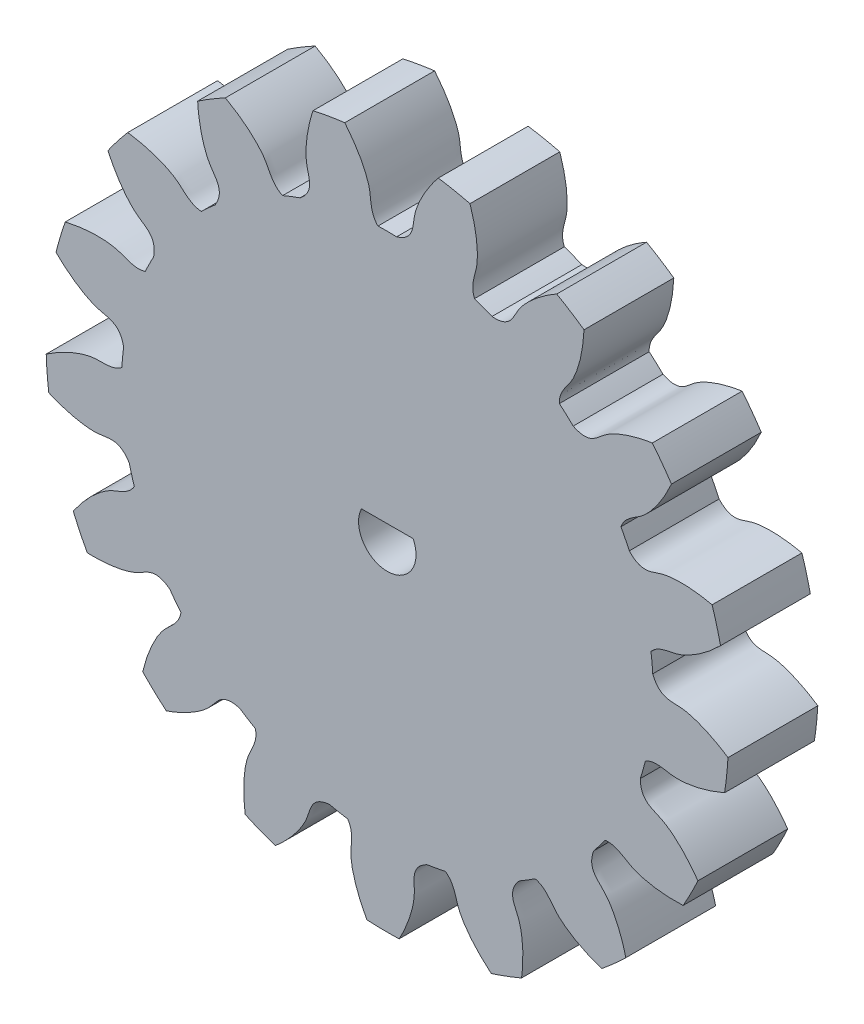
SolidWorks part; units mm, degrees
ref_plane "前视基准面" through (0, 0, 0) normal (0, 0, 1) x (1, 0, 0)
ref_plane "上视基准面" through (0, 0, 0) normal (0, 1, 0) x (1, 0, 0)
ref_plane "右视基准面" through (0, 0, 0) normal (1, 0, 0) x (0, 0, -1)
sketch "草图1" plane through (0, 0, 0) normal (0, 0, 1) x (1, 0, 0)
  circle A0 centre (0, 0) radius 19
  dimension "D1" = 38
extrude "凸台-拉伸1" add sketch "草图1" along normal blind 30
ref_axis "基准轴1" through (0, 0, -1.5) along (0, 0, 1)
sketch "草图2" plane through (0, 0, 0) normal (0, 0, 1) x (1, 0, 0)
  line L0 (0, 0) -> (0, 19) construction
  line L1 (-4.3413, 11.5) -> (4.3413, 11.5) construction
  circle A0 centre (0, 0) radius 19 construction
  arc A1 (0.5201, 14.7919) -> (-0.5201, 14.7919) centre (0, 0) ccw
  arc A2 (6.4873, 21.7509) -> (-6.0014, 21.8899) centre (0, 0) ccw
  spline S0 degree 3 poles (0.5201, 14.7919) (1.5309, 15.0929) (1.3911, 15.7825) (1.541, 16.4272) (1.5544, 16.4798) (1.5705, 16.5384) (1.5895, 16.6027) (1.6118, 16.6727) (1.6375, 16.7483) (1.667, 16.8294) (1.7003, 16.9159) (1.7378, 17.0076) (1.7796, 17.1044) (1.826, 17.2061) (1.8772, 17.3127) (1.9334, 17.4239) (1.9948, 17.5396) (2.0616, 17.6597) (2.134, 17.7839) (2.2122, 17.9121) (2.2964, 18.044) (2.3868, 18.1796) (2.4835, 18.3187) (2.5867, 18.4609) (2.6966, 18.6061) (2.8134, 18.7541) (2.9371, 18.9047) (3.068, 19.0577) (3.2061, 19.2127) (3.3517, 19.3697) (3.5048, 19.5283) (3.6656, 19.6883) (3.8342, 19.8495) (4.0106, 20.0116) (4.1951, 20.1744) (4.3877, 20.3376) (4.5884, 20.501) (4.7974, 20.6642) (5.0148, 20.8271) (5.2405, 20.9893) (5.4747, 21.1505) (5.7173, 21.3109) (6.0509, 21.5195) (6.3029, 21.6769) (6.4873, 21.7509) knots 0 0 0 0 0.200836 0.205947 0.211739 0.218212 0.225367 0.233204 0.241722 0.250921 0.260802 0.271364 0.282608 0.294533 0.307139 0.320427 0.334396 0.349047 0.364379 0.380393 0.397088 0.414464 0.432522 0.451261 0.470682 0.490784 0.511568 0.533033 0.555179 0.578007 0.601516 0.625707 0.650579 0.676133 0.702368 0.729284 0.756882 0.785161 0.814122 0.843764 0.874088 0.905093 0.936779 1 1 1 1
  spline S1 degree 3 poles (-0.5201, 14.7919) (-0.9722, 15.2536) (-0.8793, 15.8557) (-1.0122, 16.4272) (-1.0255, 16.4798) (-1.0416, 16.5384) (-1.0607, 16.6027) (-1.083, 16.6727) (-1.1087, 16.7483) (-1.1381, 16.8294) (-1.1715, 16.9159) (-1.2089, 17.0076) (-1.2508, 17.1044) (-1.2972, 17.2061) (-1.3484, 17.3127) (-1.4046, 17.4239) (-1.466, 17.5396) (-1.5328, 17.6597) (-1.6052, 17.7839) (-1.6834, 17.9121) (-1.7676, 18.044) (-1.858, 18.1796) (-1.9547, 18.3187) (-2.0579, 18.4609) (-2.1678, 18.6061) (-2.2845, 18.7541) (-2.4083, 18.9047) (-2.5391, 19.0577) (-2.6773, 19.2127) (-2.8229, 19.3697) (-2.976, 19.5283) (-3.1368, 19.6883) (-3.3053, 19.8495) (-3.4818, 20.0116) (-3.6663, 20.1744) (-3.8588, 20.3376) (-4.0596, 20.501) (-4.2686, 20.6642) (-4.4859, 20.8271) (-4.7117, 20.9892) (-4.9458, 21.1507) (-5.1889, 21.3102) (-5.5517, 21.5435) (-5.8519, 21.6965) (-6.0014, 21.8899) knots 0 0 0 0 0.178935 0.184107 0.189969 0.196521 0.203762 0.211693 0.220313 0.229623 0.239623 0.250312 0.261691 0.27376 0.286518 0.299966 0.314104 0.328931 0.344448 0.360654 0.37755 0.395136 0.413411 0.432376 0.452031 0.472375 0.493409 0.515133 0.537546 0.560649 0.584441 0.608923 0.634095 0.659956 0.686507 0.713748 0.741678 0.770298 0.799608 0.829607 0.860296 0.891674 0.923742 1 1 1 1
  point P96 (0, 14.8011)
  point P99 (0, 11.5)
  dimension "D1" = 11.5
extrude "切除-拉伸1" cut sketch "草图2" along normal through all
pattern_circular "阵列(圆周)1" count 17 every 21.176 about axis through (0, 0, -1.5) along (0, 0, 1) of "切除-拉伸1"
sketch "草图3" plane through (0, 0, 0) normal (0, 0, 1) x (1, 0, 0)
  circle A0 centre (0, 0) radius 17 construction
  dimension "Dn" = 34
sketch "草图4" plane through (0, 0, 0) normal (0, 1, 0) x (1, 0, 0)
  line L0 (18.9684, -30) -> (18.9684, 0) construction
  line L1 (-18.99, -30) -> (18.9684, -30)
  line L2 (-18.99, -30) -> (-18.99, -5)
  line L3 (-18.99, -5) -> (18.9684, -5)
  line L4 (18.9684, -30) -> (18.9684, -5)
  dimension "D1" = 25
extrude "切除-拉伸2" cut sketch "草图4" against normal through all both and the other way through all
sketch "草图5" plane through (0, 0, 5) normal (0, 0, 1) x (1, 0, 0)
  line L0 (-4.3038, -1.6) -> (4.3038, -1.6) construction
  line L1 (1.4387, 0.7) -> (-1.4387, 0.7)
  arc A0 (-1.4387, 0.7) -> (1.4387, 0.7) centre (0, 0) ccw
  point P6 (0, -1.6)
  dimension "D1" = 3.2
  dimension "D2" = 2.3
extrude "切除-拉伸3" cut sketch "草图5" against normal blind 10
